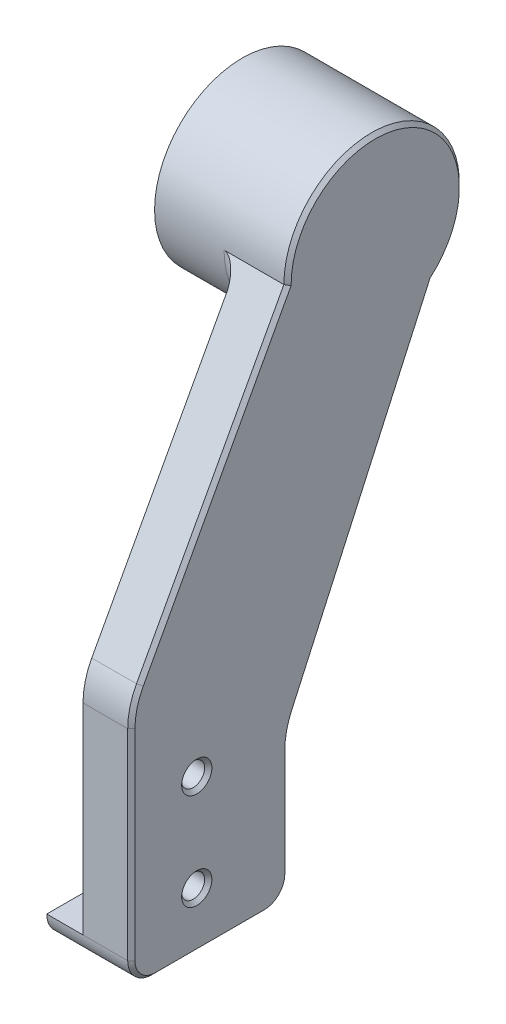
SolidWorks part; units mm, degrees
ref_plane "Front Plane" through (0, 0, 0) normal (0, 0, 1) x (1, 0, 0)
ref_plane "Top Plane" through (0, 0, 0) normal (0, 1, 0) x (1, 0, 0)
ref_plane "Right Plane" through (0, 0, 0) normal (1, 0, 0) x (0, 0, -1)
ref_plane "PX 15.420" through (15.42, 0, 0) normal (1, 0, 0) x (0, 0, -1)
sketch "cheek sketch" plane through (15.42, 0, 0) normal (1, 0, 0) x (0, 0, -1)
  line L0 (-4.37, -38) -> (-30.37, -38)
  line L1 (-30.37, -38) -> (-30.37, 2.3)
  line L2 (-30.37, 2.3) -> (-4.525, 50)
  line L3 (-4.525, 50) -> (24.525, 50)
  line L4 (24.525, 50) -> (-4.37, -13.7)
  line L5 (-4.37, -13.7) -> (-4.37, -38)
extrude "cheek" add sketch "cheek sketch" along normal mid plane 8
ref_plane "PX 8.420" through (8.42, 0, 0) normal (1, 0, 0) x (0, 0, -1)
sketch "boss sketch" plane through (8.42, 0, 0) normal (1, 0, 0) x (0, 0, -1)
  circle A0 centre (10, 50) radius 14.525
extrude "boss" add sketch "boss sketch" along normal mid plane 22
ref_plane "PX 8.670" through (8.67, 0, 0) normal (1, 0, 0) x (0, 0, -1)
sketch "lip under the leg sketch" plane through (8.67, 0, 0) normal (1, 0, 0) x (0, 0, -1)
  line L0 (-4.37, -38) -> (-4.37, -34)
  line L1 (-4.37, -34) -> (-30.37, -34)
  line L2 (-30.37, -34) -> (-30.37, -38)
  line L3 (-30.37, -38) -> (-4.37, -38)
extrude "lip under the leg" add sketch "lip under the leg sketch" along normal mid plane 6.5
ref_plane "PX 5.920" through (5.92, 0, 0) normal (1, 0, 0) x (0, 0, -1)
sketch "socket sketch" plane through (5.92, 0, 0) normal (1, 0, 0) x (0, 0, -1)
  circle A0 centre (10, 50) radius 9.775
extrude "socket" cut sketch "socket sketch" against normal mid plane 19
sketch "screw holes sketch" plane through (15.42, 0, 0) normal (1, 0, 0) x (0, 0, -1)
  circle A0 centre (-19.54, -28.7) radius 1.9
  circle A1 centre (-19.54, -12.7) radius 1.9
extrude "screw holes" cut sketch "screw holes sketch" against normal mid plane 10
fillet "cheek corners" radius 4 2 edges at (12.42, -38, 30.37) (12.42, -38, 4.37) tangent propagation no
fillet "stem blend" radius 12 2 edges at (15.42, -13.7, 4.37) (15.42, 2.3, 30.37) tangent propagation no
fillet "boss root" radius 2.5 1 edges at (11.42, 36.7723, -3.9998) tangent propagation no
chamfer "bed face chamfer" distance 0.6 angle 45 12 edges at (19.42, 63.2277, -16.0002) (19.42, 13.867, -8.1347) (19.42, -13.7586, 4.099) (19.42, -25.1472, 4.37) (19.42, -36.8284, 5.5416) (19.42, -38, 17.37) (19.42, -36.8284, 29.1984) (19.42, -17.371, 30.37) (19.42, 2.2067, 30.0021) (19.42, 27.4873, 16.7229) (19.42, -12.7, 21.44) (19.42, -28.7, 21.44)
equation "\"diffL\" = 608.8mm"
equation "\"diffW\" = 329.4mm"
equation "\"diffT\" = 2.9mm"
equation "\"chanSlotW\" = 12.9mm"
equation "\"chanSlotDepth\" = 11.13mm"
equation "\"chanFloor\" = 1.57mm"
equation "\"chanLeg\" = 12.7mm"
equation "\"lightL\" = 604.8mm"
equation "\"lightW\" = 330.2mm"
equation "\"lightH\" = 92mm"
equation "\"lightSideFlat\" = 30mm"
equation "\"lightSlopeLen\" = 38.9mm"
equation "\"lightWingDepth\" = 50.1mm"
equation "\"lightWingFlat\" = 90.2mm"
equation "\"lightChanW\" = 99.6mm"
equation "\"lightChanStand\" = 44.1mm"
equation "\"insFlangeD\" = 12.3mm"
equation "\"insFromEnd\" = 20.7mm"
equation "\"insUpSlope\" = 20.8mm"
equation "\"gaugeH\" = 10mm"
equation "\"gaugeStepLen\" = 14mm"
equation "\"gaugeStepW0\" = 13.1mm"
equation "\"gaugeStepDW\" = 0.2mm"
equation "\"gaugeSteps\" = 5mm"
equation "\"gaugeHandleLen\" = 30mm"
equation "\"gaugeHandleW\" = 24mm"
equation "\"gaugeSlot0\" = 3mm"
equation "\"gaugeSlotD\" = 0.1mm"
equation "\"gaugeSlotDepth\" = 8mm"
equation "\"gap\" = 25.4mm"
equation "\"edgeL\" = 1mm"
equation "\"edgeW\" = 0.75mm"
equation "\"proud\" = 2.5mm"
equation "\"seatClr\" = 0.15mm"
equation "\"tongueClrZ\" = 0.1mm"
equation "\"tongueClrX\" = 0.25mm"
equation "\"tongueLen\" = 30mm"
equation "\"armSide\" = 45mm"
equation "\"armEnd\" = 20mm"
equation "\"brkW\" = 26mm"
equation "\"brkT\" = 7mm"
equation "\"brkSeatClr\" = 0.3mm"
equation "\"brkScrewSpan\" = 16mm"
equation "\"pilotD\" = 4.3mm"
equation "\"pilotDepth\" = 8mm"
equation "\"screwClrD\" = 3.8mm"
equation "\"jogBelow\" = 4mm"
equation "\"padT\" = 7mm"
equation "\"padLen\" = 36mm"
equation "\"m6Clr\" = 9mm"
equation "\"m6Slot\" = 5mm"
equation "\"flangeRelD\" = 18mm"
equation "\"flangeRelDepth\" = 1.5mm"
equation "\"relLen\" = 5mm"
equation "\"relDepth\" = 3.3mm"
equation "\"knockN\" = 100mm"
equation "\"petgcfE\" = 3000mm"
equation "\"mockExtent\" = 110mm"
equation "\"relZnear\" = 9.4mm"
equation "\"relZfar\" = 23.4mm"
equation "\"headD\" = 8mm"
equation "\"headH\" = 2.5mm"
equation "\"headFromEnd\" = 6.8mm"
equation "\"headBack\" = 16.4mm"
equation "\"sideClr\" = 0.4mm"
equation "\"cornerRelR\" = 1.5mm"
equation "\"cornerRelBack\" = 0.6mm"
equation "\"endHeadH\" = 2.8mm"
equation "\"footClr\" = 1.2mm"
equation "\"footEndClr\" = 3.5mm"
equation "\"footBlockClr\" = 0.5mm"
equation "\"footBack\" = 85mm"
equation "\"footFwd\" = 10mm"
equation "\"footBraceEnd\" = 3mm"
equation "\"spacerLen\" = 60mm"
equation "\"spacerShort\" = 0.5mm"
equation "\"spacerCham\" = 0.8mm"
equation "\"spacerPerSide\" = 3mm"
equation "\"spacerPerEnd\" = 1mm"
equation "\"toolR\" = 9mm"
equation "\"visR\" = 4mm"
equation "\"edgeR\" = 1mm"
equation "\"bendOutR\" = 5mm"
equation "\"insideR\" = 2.5mm"
equation "\"footCornerR\" = 10mm"
equation "\"footFrontR\" = 8mm"
equation "\"braceKinkR\" = 12mm"
equation "\"bedCham\" = 1mm"
equation "\"bedChamSmall\" = 0.6mm"
equation "\"soleTopR\" = 2mm"
equation "\"cornerR\" = 6mm"
equation "\"rimInR\" = 1mm"
equation "\"insFlangeH\" = 1mm"
equation "\"insHoleFinishD\" = 4.5mm"
equation "\"insLen\" = 6.4mm"
equation "\"cgInset\" = 4mm"
equation "\"lampWeightN\" = 51mm"
equation "\"frameWeightN\" = 10mm"
equation "\"bumpIn\" = 8mm"
equation "\"bumpH\" = 3mm"
equation "\"legBelowFront\" = 2mm"
equation "\"lipClr\" = 0.1mm"
equation "\"revealR\" = 2mm"
equation "\"frontCham\" = 1mm"
equation "\"leanDeg\" = 5mm"
equation "\"footTailT\" = 6mm"
equation "\"v1LeanDeg\" = 4.5mm"
equation "\"toeNoseR\" = 5mm"
equation "\"petgE\" = 2000mm"
equation "\"cheekT\" = 8mm"
equation "\"handleUp\" = 50mm"
equation "\"handleZ\" = -10mm"
equation "\"gripD\" = 19.05mm"
equation "\"gripClr\" = 0.5mm"
equation "\"bossWall\" = 5mm"
equation "\"bossLen\" = 14mm"
equation "\"socketFloor\" = 4mm"
equation "\"barEndClr\" = 1mm"
equation "\"lipH\" = 4mm"
equation "\"lipDeep\" = 6mm"
